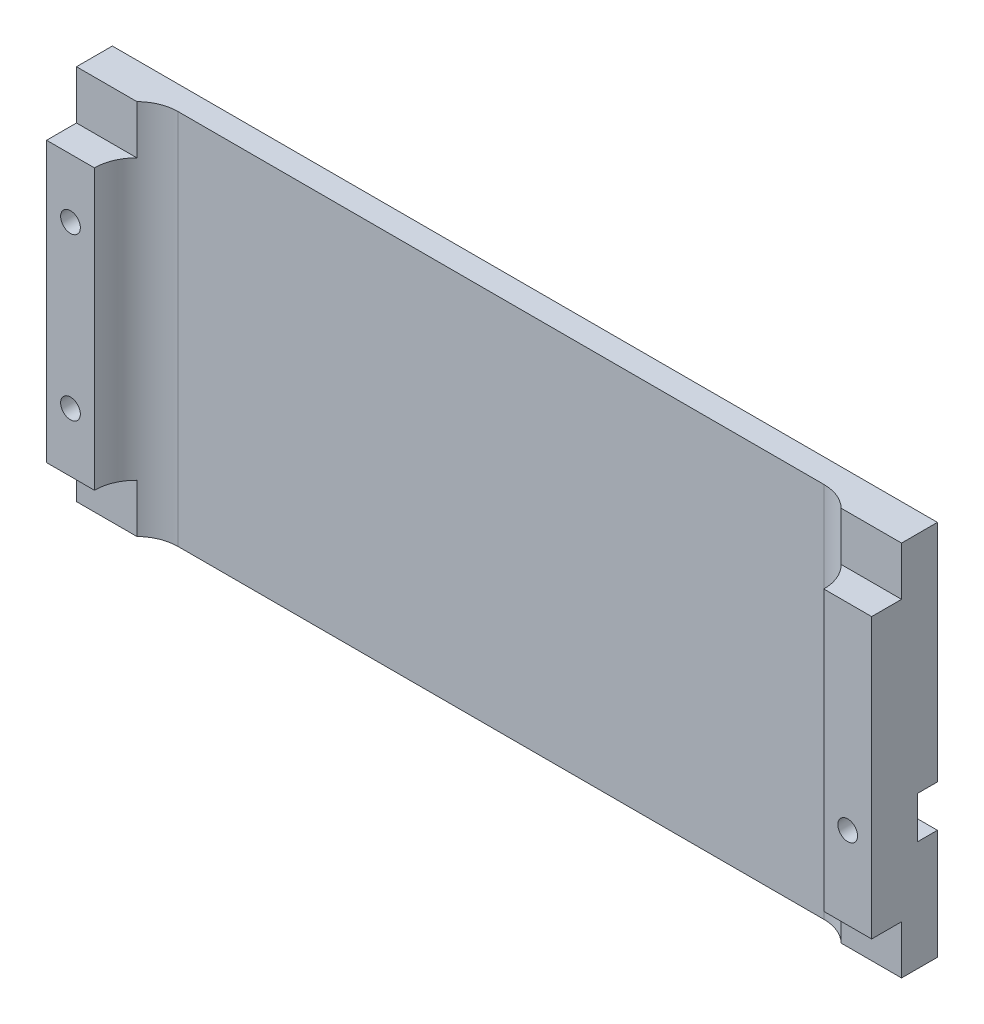
SolidWorks part; units mm, degrees
ref_plane "Plano frontal" through (0, 0, 0) normal (0, 0, 1) x (1, 0, 0)
ref_plane "Plano superior" through (0, 0, 0) normal (0, 1, 0) x (1, 0, 0)
ref_plane "Plano direito" through (0, 0, 0) normal (1, 0, 0) x (0, 0, -1)
sketch "Esboço1" plane through (0, 0, 0) normal (0, 0, 1) x (1, 0, 0)
  line L1 (69, -31.5) -> (-69, -31.5)
  line L2 (69, -31.5) -> (69, 31.5)
  line L3 (69, 31.5) -> (-69, 31.5)
  line L4 (-69, -31.5) -> (-69, 31.5)
  line L5 (69, -31.5) -> (-69, 31.5) construction
  line L6 (69, 31.5) -> (-69, -31.5) construction
  point P0 (0, 0)
  dimension "D1" = 63
  dimension "D2" = 138
extrude "Ressalto-extrusão1" add sketch "Esboço1" along normal blind 4
sketch "Esboço2" plane through (0, 0, 4) normal (0, 0, 1) x (1, 0, 0)
  line L0 (-69, -31.5) -> (69, -31.5) construction
  line L1 (69, 31.5) -> (61, 31.5)
  line L2 (69, 31.5) -> (69, -31.5)
  line L3 (69, -31.5) -> (61, -31.5)
  line L4 (61, 31.5) -> (61, -31.5)
  line L5 (65, -31.5) -> (65, 31.5) construction
  line L6 (69, 0) -> (61, 0) construction
  line L8 (-69, 31.5) -> (-61, 31.5)
  line L9 (-69, 31.5) -> (-69, -31.5)
  line L10 (-69, -31.5) -> (-61, -31.5)
  line L11 (-61, 31.5) -> (-61, -31.5)
  line L12 (-65, -31.5) -> (-65, 31.5) construction
  line L13 (-69, 0) -> (-61, 0) construction
  point P236 (65, 0)
  point P268 (-65, 0)
  dimension "D1" = 8
  dimension "D2" = 8
extrude "Ressalto-extrusão2" add sketch "Esboço2" along normal blind 2
sketch "Esboço3" plane through (0, 0, 6) normal (0, 0, 1) x (1, 0, 0)
  line L0 (61, 31.5) -> (61, -31.5) construction
  line L1 (61, 23.35) -> (69, 23.35)
  line L2 (61, 23.35) -> (61, -23.35)
  line L3 (61, -23.35) -> (69, -23.35)
  line L4 (69, 23.35) -> (69, -23.35)
  line L5 (65, -23.35) -> (65, 23.35) construction
  line L6 (61, 0) -> (69, 0) construction
  line L7 (69, -31.5) -> (69, 31.5) construction
  line L8 (61, -31.5) -> (69, -31.5) construction
  line L9 (69, 31.5) -> (61, 31.5) construction
  line L10 (-69, 31.5) -> (-69, -31.5) construction
  line L11 (-69, 23.35) -> (-61, 23.35)
  line L12 (-69, 23.35) -> (-69, -23.35)
  line L13 (-69, -23.35) -> (-61, -23.35)
  line L14 (-61, 23.35) -> (-61, -23.35)
  line L15 (-65, -23.35) -> (-65, 23.35) construction
  line L16 (-69, 0) -> (-61, 0) construction
  line L17 (-61, -31.5) -> (-61, 31.5) construction
  line L18 (-69, -31.5) -> (-61, -31.5) construction
  line L19 (-61, 31.5) -> (-69, 31.5) construction
  point P296 (65, 0)
  point P421 (-65, 0)
  dimension "D1" = 8.15
  dimension "D2" = 8.15
  dimension "D3" = 8.15
  dimension "D4" = 8.15
extrude "Ressalto-extrusão3" add sketch "Esboço3" along normal blind 5
sketch "Esboço4" plane through (0, 0, 0) normal (0, 0, -1) x (-1, 0, 0)
  line L0 (69, -31.5) -> (-69, -31.5) construction
  line L1 (69, 31.5) -> (69, -31.5) construction
  line L2 (-69, 31.5) -> (69, 31.5) construction
  line L3 (-69, -31.5) -> (-69, 31.5) construction
  circle A0 centre (65, -13.5) radius 1.65
  circle A1 centre (65, 13.5) radius 1.65
  circle A2 centre (-65, -9.6) radius 1.65
  dimension "D3" = 3.3
  dimension "D4" = 4
  dimension "D6" = 3.3
  dimension "D8" = 4
  dimension "D9" = 3.3
  dimension "D1" = 18
  dimension "D2" = 4
  dimension "D5" = 18
  dimension "D7" = 21.9
extrude "Corte-extrusão1" cut sketch "Esboço4" against normal through all
sketch "Esboço5" plane through (0, 0, 0) normal (0, 0, -1) x (-1, 0, 0)
  line L0 (65, -17) -> (69, -17)
  line L1 (69, 31.5) -> (69, -31.5) construction
  line L2 (69, -17) -> (69, -10)
  line L3 (69, -10) -> (65, -10)
  line L5 (65, 10) -> (69, 10)
  line L6 (69, 10) -> (69.1487, 17)
  line L7 (69.1487, 17) -> (65, 17)
  line L10 (-65, -6.1) -> (-69, -6.1)
  line L11 (-69, -31.5) -> (-69, 31.5) construction
  line L12 (-69, -6.1) -> (-69, -13.1)
  line L13 (-69, -13.1) -> (-65, -13.1)
  arc A0 (65, -10) -> (65, -17) centre (65, -13.5) ccw
  arc A1 (65, 17) -> (65, 10) centre (65, 13.5) ccw
  arc A2 (-65, -13.1) -> (-65, -6.1) centre (-65, -9.6) ccw
  dimension "D1" = 7
  dimension "D2" = 7
  dimension "D3" = 7
extrude "Corte-extrusão2" cut sketch "Esboço5" against normal blind 3.3
fillet "Filete1" radius 7 2 edges at (61, 0, 4) (-61, 0, 4)
